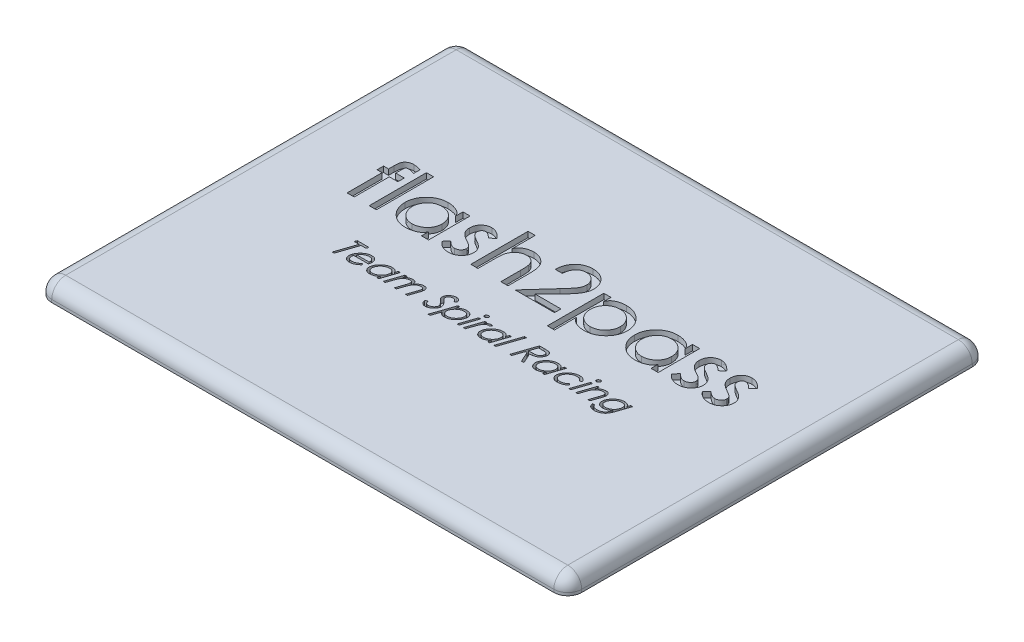
SolidWorks part; units mm, degrees
ref_plane "Front Plane" through (0, 0, 0) normal (0, 0, 1) x (1, 0, 0)
ref_plane "Top Plane" through (0, 0, 0) normal (0, 1, 0) x (1, 0, 0)
ref_plane "Right Plane" through (0, 0, 0) normal (1, 0, 0) x (0, 0, -1)
sketch "Sketch2" plane through (0, 0, 0) normal (0, 1, 0) x (1, 0, 0)
  line L1 (-47.5, 37.5) -> (47.5, 37.5)
  line L2 (-47.5, 37.5) -> (-47.5, -37.5)
  line L3 (-47.5, -37.5) -> (47.5, -37.5)
  line L4 (47.5, 37.5) -> (47.5, -37.5)
  point P4 (47.5, 0)
  point P5 (0, -37.5)
  point P7 (92.2857, -47.5)
  dimension "D1" = 75
  dimension "D2" = 95
extrude "Boss-Extrude1" add sketch "Sketch2" along normal mid plane 5.5
sketch "Sketch3" plane through (0, -2.75, 0) normal (0, -1, 0) x (1, 0, 0)
  line L1 (-47.5, -37.5) -> (47.5, -37.5)
  line L2 (-47.5, -37.5) -> (-47.5, 37.5)
  line L3 (-47.5, 37.5) -> (47.5, 37.5)
  line L4 (47.5, -37.5) -> (47.5, 37.5)
  line L5 (-45, -35) -> (45, -35)
  line L6 (-45, -35) -> (-45, 35)
  line L7 (-45, 35) -> (45, 35)
  line L8 (45, -35) -> (45, 35)
  circle A0 centre (-41.5, 32.5) radius 1.75
  circle A1 centre (41.5, 32.5) radius 1.75
  circle A2 centre (41.5, -32.5) radius 1.75
  circle A3 centre (-41.5, -32.5) radius 1.75
  point P18 (0, 0)
  point P21 (-8.6187, -9.7826)
  line M9 (-47.5, 37.5) -> (-47.5, -37.5)
  line M10 (-47.5, -37.5) -> (47.5, -37.5)
  line M11 (47.5, -37.5) -> (47.5, 37.5)
  line M12 (47.5, 37.5) -> (-47.5, 37.5)
  dimension "D7" = 3.5
  dimension "D10" = 3.5
  dimension "D13" = 3.5
  dimension "D16" = 3.5
  dimension "D1" = 2.5
  dimension "D2" = 2.5
  dimension "D3" = 2.5
  dimension "D4" = 2.5
  dimension "D5" = 3.5
  dimension "D6" = 2.5
  dimension "D8" = 3.5
  dimension "D9" = 2.5
  dimension "D11" = 3.5
  dimension "D12" = 2.5
  dimension "D14" = 2.5
  dimension "D15" = 3.5
extrude "Cut-Extrude1" cut sketch "Sketch3" against normal blind 2.5 contours L8 L5 L6 L7 M12 M9 M10 M11 | A3 | A0 | A2 | A1 region at (-46.2896, -2.75, 0) region at (-41.5, -2.75, 32.5) region at (41.5, -2.75, 32.5) region at (41.5, -2.75, -32.5) region at (-41.5, -2.75, -32.5)
fillet "Fillet4" radius 2.5 4 edges at (-47.5, 2.75, 0) (0, 2.75, 37.5) (47.5, 2.75, 0) (0, 2.75, -37.5) type face fillet first side face at (-47.5, 1.25, 0) first side face at (0, 1.25, -37.5) first side face at (47.5, 1.25, 0) first side face at (0, 1.25, 37.5) second side face at (0, 2.75, 0)
fillet "Fillet5" radius 2.5 1 edges at (-47.5, 0, 37.5) type face fillet first side face at (-47.5, 0, 0) second side face at (0, 0, 37.5)
fillet "Fillet6" radius 2.5 1 edges at (47.5, 0, 37.5) type face fillet first side face at (1.25, 0, 37.5) second side face at (47.5, 0, 0)
fillet "Fillet7" radius 2.5 1 edges at (47.5, 0, -37.5) type face fillet first side face at (47.5, 0, -1.25) second side face at (0, 0, -37.5)
fillet "Fillet8" radius 2.5 1 edges at (-47.5, 0, -37.5) type face fillet first side face at (-1.25, 0, -37.5) second side face at (-47.5, 0, -1.25)
fillet "Fillet9" radius 1 4 edges at (45, -2.75, 0) (0, -2.75, 35) (-45, -2.75, 0) (0, -2.75, -35) type face fillet first side face at (0, -1.5, 35) first side face at (45, -1.5, 0) first side face at (-45, -1.5, 0) first side face at (0, -1.5, -35) second side face at (41.5, -2.75, 30.75)
fillet "Fillet10" radius 1 1 edges at (45, -1, -35) type face fillet first side face at (45, -1, 0) second side face at (0, -1, -35)
fillet "Fillet11" radius 1 1 edges at (-45, -1, -35) type face fillet first side face at (-0.5, -1, -35) second side face at (-45, -1, 0)
fillet "Fillet12" radius 1 1 edges at (-45, -1, 35) type face fillet first side face at (-45, -1, 0.5) second side face at (0, -1, 35)
fillet "Fillet13" radius 1 1 edges at (45, -1, 35) type face fillet first side face at (0.5, -1, 35) second side face at (45, -1, 0.5)
sketch "Sketch4" plane through (0, 2.75, 0) normal (0, 1, 0) x (1, 0, 0)
  line L0 (-35, 3) -> (35, 3) construction
  line L1 (-45, 35) -> (-45, -35) construction
  line L2 (-35, -7.5) -> (35, -7.5) construction
  text T0 "<b>flash2pass</b>" font "Century Gothic" height 10
  text T1 "<i>Team Spiral Racing</i>" font "Century Gothic" height 4
  point P2 (0, 0)
  point P3 (-5.8308, -2.6344)
  point P4 (0, 0)
  point P5 (0, 0)
  point P12 (0, 0)
  point P13 (0, -7.5)
  dimension "D1" = 10
  dimension "D2" = 3
  dimension "D3" = 10
  dimension "D4" = 7.5
extrude "Cut-Extrude2" cut sketch "Sketch4" against normal blind 1
